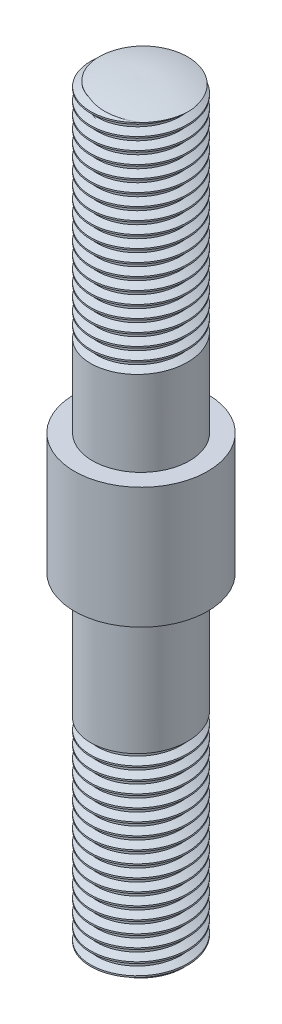
SolidWorks part; units mm, degrees
ref_plane "Front Plane" through (0, 0, 0) normal (0, 0, 1) x (1, 0, 0)
ref_plane "Top Plane" through (0, 0, 0) normal (0, 1, 0) x (1, 0, 0)
ref_plane "Right Plane" through (0, 0, 0) normal (1, 0, 0) x (0, 0, -1)
sketch "Sketch1" plane through (0, 0, 0) normal (0, 0, 1) x (1, 0, 0)
  line L0 (0, 0) -> (0, 125) construction
  line L1 (0, 0) -> (-30.3047, 0) construction
  line L2 (-8, 1.3146) -> (-8, 54)
  line L3 (-8, 54) -> (-11, 54)
  line L4 (-11, 54) -> (-11, 74)
  line L5 (-11, 74) -> (-8, 74)
  line L6 (-8, 74) -> (-8, 124.02)
  line L7 (-9.4712, 125.02) -> (-25.6131, 125.02) construction
  line L8 (0, 0) -> (0, 125)
  arc A0 (0, 0) -> (-8, 1.3146) centre (0, 25) cw
  arc A1 (-8, 124.02) -> (0, 125) centre (-1, 100.02) cw
  dimension "D6" = 25
  dimension "D1" = 125
  dimension "D2" = 16
  dimension "D3" = 54
  dimension "D4" = 22
  dimension "D5" = 20
  dimension "D7" = 1
revolve "Revolve1" add sketch "Sketch1" angle 360 about L8
thread "Thread1" pitch 2 method cut profile "Thread Profile1" start angle 0, offset 3, length 35, pitch 2, diameter 16
ref_plane "Plane1" through (8, -1.6854, 0) normal (0, 0, 1) x (1, 0, 0)
sketch "Thread Profile1" plane through (8, -1.6854, 0) normal (0, 0, 1) x (1, 0, 0)
  line L0 (0, 0) -> (0, 2) construction
  line L11 (0, 0) -> (0, 1.75)
  line L12 (0, 1.75) -> (-1.0825, 1.125)
  line L13 (-1.0825, 1.125) -> (-1.0825, 0.625)
  line L15 (-1.0825, 0.625) -> (0, 0)
  line L17 (-1.0825, 0.875) -> (0, 0.875) construction
  point P2 (0, 0)
  dimension "Pitch" = 2
  dimension "Profile_Angle" = 60
  dimension "Profile_Land" = 0.5
  dimension "Profile_Height" = 1.0825
thread "Thread2" pitch 2 method cut profile "Thread Profile2" start angle 0, offset 3, length 38, pitch 2, diameter 16
ref_plane "Plane2" through (-8, 127.02, 0) normal (0, 0, 1) x (-1, 0, 0)
sketch "Thread Profile2" plane through (-8, 127.02, 0) normal (0, 0, 1) x (-1, 0, 0)
  line L0 (0, 0) -> (0, 2) construction
  line L11 (0, 0) -> (0, 1.75)
  line L12 (0, 1.75) -> (-1.0825, 1.125)
  line L13 (-1.0825, 1.125) -> (-1.0825, 0.625)
  line L15 (-1.0825, 0.625) -> (0, 0)
  line L17 (-1.0825, 0.875) -> (0, 0.875) construction
  point P2 (0, 0)
  dimension "Pitch" = 2
  dimension "Profile_Angle" = 60
  dimension "Profile_Land" = 0.5
  dimension "Profile_Height" = 1.0825
